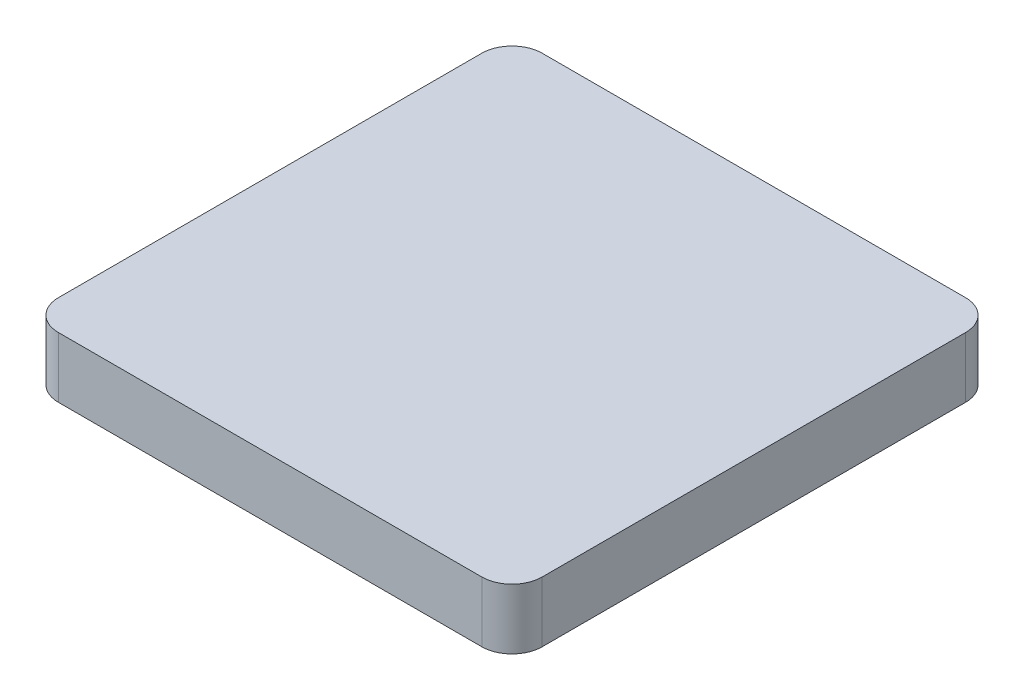
SolidWorks part; units mm, degrees
ref_plane "Plan de face" through (0, 0, 0) normal (0, 0, 1) x (1, 0, 0)
ref_plane "Plan de dessus" through (0, 0, 0) normal (0, 1, 0) x (1, 0, 0)
ref_plane "Plan de droite" through (0, 0, 0) normal (1, 0, 0) x (0, 0, -1)
sketch "Esquisse1" plane through (0, 0, 0) normal (0, 1, 0) x (1, 0, 0)
  line L1 (0, 0) -> (80, 0)
  line L2 (0, 0) -> (0, 80)
  line L3 (0, 80) -> (80, 80)
  line L4 (80, 0) -> (80, 80)
  dimension "D1" = 80
  dimension "D2" = 80
extrude "Extrusion1" add sketch "Esquisse1" along normal blind 10
sketch "Esquisse2" plane through (0, 0, 0) normal (0, -1, 0) x (1, 0, 0)
  line L0 (80, 0) -> (80, -80) construction
  line L1 (11.5, -34.5) -> (36, -34.5)
  line L2 (11.5, -34.5) -> (11.5, -45.5)
  line L3 (11.5, -45.5) -> (36, -45.5)
  line L4 (36, -34.5) -> (36, -45.5)
  line L5 (0, -80) -> (0, 0) construction
  line L6 (0, 0) -> (80, 0) construction
  dimension "D1" = 11
  dimension "D2" = 44
  dimension "D3" = 11.5
  dimension "D4" = 34.5
extrude "Enlèv. mat.-Extru.1" cut sketch "Esquisse2" against normal blind 8
chamfer "Chanfrein1" distance 8 angle 45 1 edges at (11.5, 0, -40)
chamfer "Chanfrein2" distance 8 angle 45 1 edges at (36, 0, -40)
fillet "Congé1" radius 5 4 edges at (80, 5, -80) (0, 5, -80) (0, 5, 0) (80, 5, 0)
sketch "Esquisse3" plane through (0, 0, 0) normal (0, -1, 0) x (1, 0, 0)
  line L1 (44, -37.5) -> (49, -37.5)
  line L2 (44, -37.5) -> (44, -42.5)
  line L3 (44, -42.5) -> (49, -42.5)
  line L4 (49, -37.5) -> (49, -42.5)
  line L5 (80, -5) -> (80, -75) construction
  line L6 (5, 0) -> (75, 0) construction
  dimension "D1" = 5
  dimension "D2" = 5
  dimension "D3" = 31
  dimension "D4" = 37.5
extrude "Enlèv. mat.-Extru.2" cut sketch "Esquisse3" against normal blind 5
